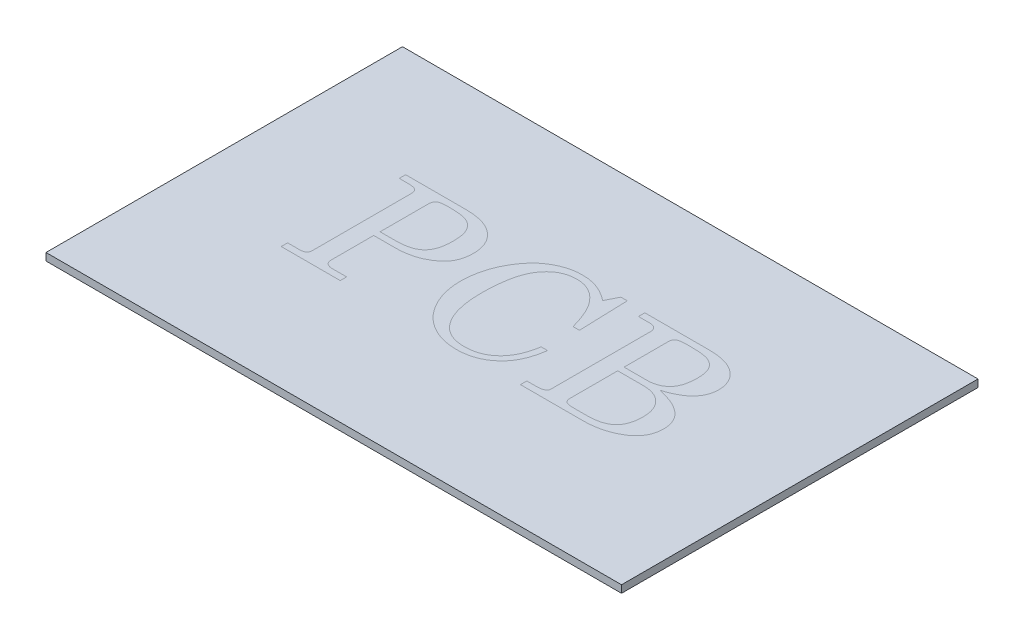
SolidWorks part; units mm, degrees
ref_plane "Front Plane" through (0, 0, 0) normal (0, 0, 1) x (1, 0, 0)
ref_plane "Top Plane" through (0, 0, 0) normal (0, 1, 0) x (1, 0, 0)
ref_plane "Right Plane" through (0, 0, 0) normal (1, 0, 0) x (0, 0, -1)
sketch "Sketch1" plane through (0, 0, 0) normal (0, 1, 0) x (1, 0, 0)
  line L1 (-77.5, -48) -> (77.5, -48)
  line L2 (-77.5, -48) -> (-77.5, 48)
  line L3 (-77.5, 48) -> (77.5, 48)
  line L4 (77.5, -48) -> (77.5, 48)
  line L5 (-77.5, -48) -> (77.5, 48) construction
  line L6 (-77.5, 48) -> (77.5, -48) construction
  point P0 (0, 0)
  dimension "D1" = 155
  dimension "D2" = 96
extrude "Boss-Extrude1" add sketch "Sketch1" along normal blind 2
sketch "Sketch2" plane through (0, 2, 0) normal (0, 1, 0) x (1, 0, 0)
  text T0 "PCB" font "Century Schoolbook" height 33.5
wrap "Wrap1" sketch "Sketch2" wrap type scribe source sketch "Sketch2" face at (0, 2, 0)
